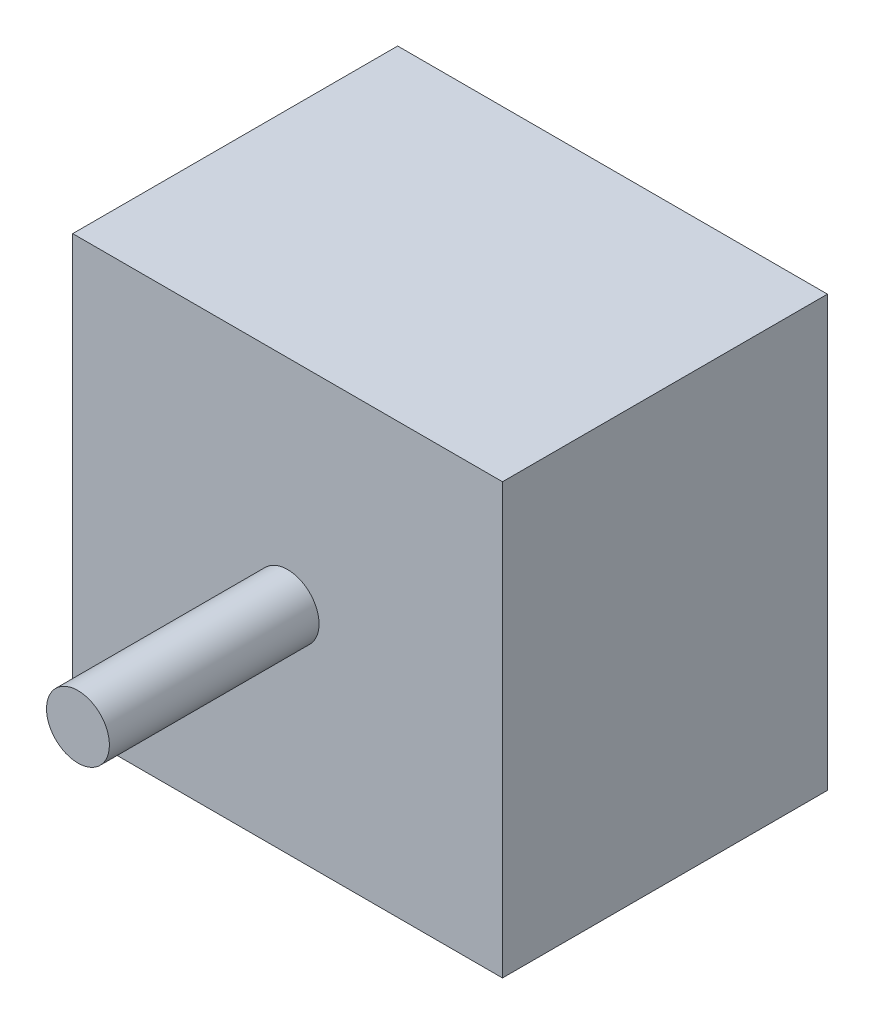
SolidWorks part; units mm, degrees
ref_plane "Front Plane" through (0, 0, 0) normal (0, 0, 1) x (1, 0, 0)
ref_plane "Top Plane" through (0, 0, 0) normal (0, 1, 0) x (1, 0, 0)
ref_plane "Right Plane" through (0, 0, 0) normal (1, 0, 0) x (0, 0, -1)
sketch "Sketch1" plane through (0, 0, 0) normal (0, 0, 1) x (1, 0, 0)
  line L1 (20.5, -20.5) -> (-20.5, -20.5)
  line L2 (20.5, -20.5) -> (20.5, 20.5)
  line L3 (20.5, 20.5) -> (-20.5, 20.5)
  line L4 (-20.5, -20.5) -> (-20.5, 20.5)
  line L5 (20.5, -20.5) -> (-20.5, 20.5) construction
  line L6 (20.5, 20.5) -> (-20.5, -20.5) construction
  circle A0 centre (0, 0) radius 3
  point P0 (0, 0)
  dimension "D3" = 6
  dimension "D1" = 41
  dimension "D2" = 41
extrude "Boss-Extrude1" add sketch "Sketch1" along normal blind 31
extrude "Boss-Extrude2" add sketch "Sketch1<2>" along normal blind 51 contours A0 region at (0, 0, 0)
sketch "Sketch1<2>" plane through (0, 0, 0) normal (0, 0, 1) x (1, 0, 0) same geometry as "Sketch1"
